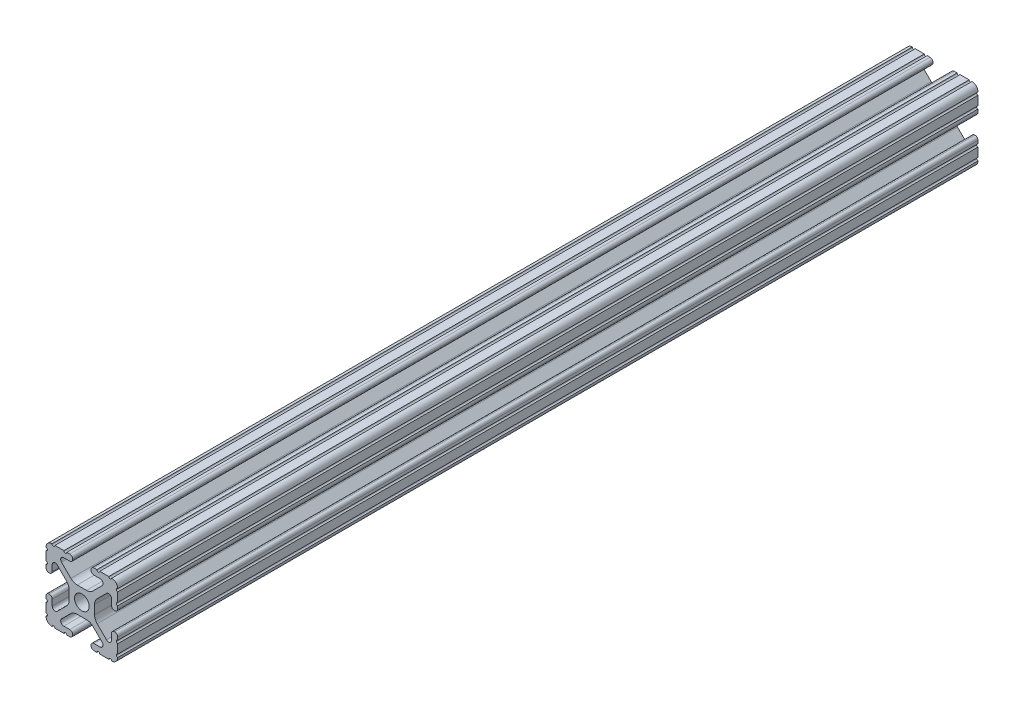
SolidWorks part; units mm, degrees
material "6061 Alloy"
ref_plane "Front Plane" through (0, 0, 0) normal (0, 0, 1) x (1, 0, 0)
ref_plane "Top Plane" through (0, 0, 0) normal (0, 1, 0) x (1, 0, 0)
ref_plane "Right Plane" through (0, 0, 0) normal (1, 0, 0) x (0, 0, -1)
sketch "Sketch1" plane through (0, 0, 0) normal (0, 0, 1) x (1, 0, 0)
  line L88 (-7.1797, -8.6452) -> (-3.9523, -5.4237)
  line L89 (-1.7093, -4.4958) -> (1.7093, -4.4958)
  line L90 (3.9523, -5.4237) -> (7.1797, -8.6452)
  line L91 (6.4164, -10.4902) -> (4.2875, -10.4902)
  line L92 (3.2385, -11.5392) -> (3.2385, -11.651)
  line L93 (4.2875, -12.7) -> (5.3171, -12.7)
  line L94 (6.3331, -12.7) -> (9.5504, -12.7)
  line L95 (12.7, -9.5504) -> (12.7, -6.3331)
  line L96 (12.7, -5.3171) -> (12.7, -4.2875)
  line L97 (11.651, -3.2385) -> (11.5392, -3.2385)
  line L98 (10.4902, -4.2875) -> (10.4902, -6.4021)
  line L99 (8.7371, -7.1294) -> (5.441, -3.8408)
  line L100 (4.5085, -1.5932) -> (4.5085, 1.5932)
  line L101 (5.441, 3.8408) -> (8.7371, 7.1294)
  line L102 (10.4902, 6.4021) -> (10.4902, 4.2875)
  line L103 (11.5392, 3.2385) -> (11.651, 3.2385)
  line L104 (12.7, 4.2875) -> (12.7, 5.3171)
  line L105 (12.7, 6.3331) -> (12.7, 9.5504)
  line L106 (9.5504, 12.7) -> (6.3331, 12.7)
  line L107 (5.3171, 12.7) -> (4.2875, 12.7)
  line L108 (3.2385, 11.651) -> (3.2385, 11.5392)
  line L109 (4.2875, 10.4902) -> (6.4768, 10.4902)
  line L110 (7.207, 8.7244) -> (3.8983, 5.4232)
  line L111 (1.6558, 4.4958) -> (-1.6558, 4.4958)
  line L112 (-3.8983, 5.4232) -> (-7.207, 8.7244)
  line L113 (-6.4768, 10.4902) -> (-4.2875, 10.4902)
  line L114 (-3.2385, 11.5392) -> (-3.2385, 11.651)
  line L115 (-4.2875, 12.7) -> (-5.3171, 12.7)
  line L116 (-6.3331, 12.7) -> (-9.5504, 12.7)
  line L117 (-12.7, 9.5504) -> (-12.7, 6.3331)
  line L118 (-12.7, 5.3171) -> (-12.7, 4.2875)
  line L119 (-11.651, 3.2385) -> (-11.5392, 3.2385)
  line L120 (-10.4902, 4.2875) -> (-10.4902, 6.4021)
  line L121 (-8.7371, 7.1294) -> (-5.441, 3.8408)
  line L122 (-4.5085, 1.5932) -> (-4.5085, -1.5932)
  line L123 (-5.441, -3.8408) -> (-8.7371, -7.1294)
  line L124 (-10.4902, -6.4021) -> (-10.4902, -4.2875)
  line L125 (-11.5392, -3.2385) -> (-11.651, -3.2385)
  line L126 (-12.7, -4.2875) -> (-12.7, -5.3171)
  line L127 (-12.7, -6.3331) -> (-12.7, -9.5504)
  line L128 (-9.5504, -12.7) -> (-6.3331, -12.7)
  line L129 (-5.3171, -12.7) -> (-4.2875, -12.7)
  line L130 (-3.2385, -11.651) -> (-3.2385, -11.5392)
  line L131 (-4.2875, -10.4902) -> (-6.4164, -10.4902)
  circle A1 centre (0, 0) radius 2.6035
  arc A104 (-7.1797, -8.6452) -> (-6.4164, -10.4902) centre (-6.4164, -9.4098) ccw
  arc A105 (-1.7093, -4.4958) -> (-3.9523, -5.4237) centre (-1.7093, -7.6708) ccw
  arc A106 (3.9523, -5.4237) -> (1.7093, -4.4958) centre (1.7093, -7.6708) ccw
  arc A107 (6.4164, -10.4902) -> (7.1797, -8.6452) centre (6.4164, -9.4098) ccw
  arc A108 (4.2875, -10.4902) -> (3.2385, -11.5392) centre (4.2875, -11.5392) ccw
  arc A109 (3.2385, -11.651) -> (4.2875, -12.7) centre (4.2875, -11.651) ccw
  arc A110 (6.3331, -12.7) -> (5.3171, -12.7) centre (5.8251, -12.7) ccw
  arc A111 (10.5664, -12.6998) -> (9.5504, -12.7) centre (10.0584, -12.7) ccw
  arc A112 (10.5664, -12.6998) -> (12.6998, -10.5664) centre (10.5918, -10.5918) ccw
  arc A113 (12.7, -9.5504) -> (12.6998, -10.5664) centre (12.7, -10.0584) ccw
  arc A114 (12.7, -5.3171) -> (12.7, -6.3331) centre (12.7, -5.8251) ccw
  arc A115 (12.7, -4.2875) -> (11.651, -3.2385) centre (11.651, -4.2875) ccw
  arc A116 (11.5392, -3.2385) -> (10.4902, -4.2875) centre (11.5392, -4.2875) ccw
  arc A117 (8.7371, -7.1294) -> (10.4902, -6.4021) centre (9.4628, -6.4021) ccw
  arc A118 (4.5085, -1.5932) -> (5.441, -3.8408) centre (7.6835, -1.5932) ccw
  arc A119 (5.441, 3.8408) -> (4.5085, 1.5932) centre (7.6835, 1.5932) ccw
  arc A120 (10.4902, 6.4021) -> (8.7371, 7.1294) centre (9.4628, 6.4021) ccw
  arc A121 (10.4902, 4.2875) -> (11.5392, 3.2385) centre (11.5392, 4.2875) ccw
  arc A122 (11.651, 3.2385) -> (12.7, 4.2875) centre (11.651, 4.2875) ccw
  arc A123 (12.7, 6.3331) -> (12.7, 5.3171) centre (12.7, 5.8251) ccw
  arc A124 (12.6998, 10.5664) -> (12.7, 9.5504) centre (12.7, 10.0584) ccw
  arc A125 (12.6998, 10.5664) -> (10.5664, 12.6998) centre (10.5918, 10.5918) ccw
  arc A126 (9.5504, 12.7) -> (10.5664, 12.6998) centre (10.0584, 12.7) ccw
  arc A127 (5.3171, 12.7) -> (6.3331, 12.7) centre (5.8251, 12.7) ccw
  arc A128 (4.2875, 12.7) -> (3.2385, 11.651) centre (4.2875, 11.651) ccw
  arc A129 (3.2385, 11.5392) -> (4.2875, 10.4902) centre (4.2875, 11.5392) ccw
  arc A130 (7.207, 8.7244) -> (6.4768, 10.4902) centre (6.4768, 9.4563) ccw
  arc A131 (1.6558, 4.4958) -> (3.8983, 5.4232) centre (1.6558, 7.6708) ccw
  arc A132 (-3.8983, 5.4232) -> (-1.6558, 4.4958) centre (-1.6558, 7.6708) ccw
  arc A133 (-6.4768, 10.4902) -> (-7.207, 8.7244) centre (-6.4768, 9.4563) ccw
  arc A134 (-4.2875, 10.4902) -> (-3.2385, 11.5392) centre (-4.2875, 11.5392) ccw
  arc A135 (-3.2385, 11.651) -> (-4.2875, 12.7) centre (-4.2875, 11.651) ccw
  arc A136 (-6.3331, 12.7) -> (-5.3171, 12.7) centre (-5.8251, 12.7) ccw
  arc A137 (-10.5664, 12.6998) -> (-9.5504, 12.7) centre (-10.0584, 12.7) ccw
  arc A138 (-10.5664, 12.6998) -> (-12.6998, 10.5664) centre (-10.5918, 10.5918) ccw
  arc A139 (-12.7, 9.5504) -> (-12.6998, 10.5664) centre (-12.7, 10.0584) ccw
  arc A140 (-12.7, 5.3171) -> (-12.7, 6.3331) centre (-12.7, 5.8251) ccw
  arc A141 (-12.7, 4.2875) -> (-11.651, 3.2385) centre (-11.651, 4.2875) ccw
  arc A142 (-11.5392, 3.2385) -> (-10.4902, 4.2875) centre (-11.5392, 4.2875) ccw
  arc A143 (-8.7371, 7.1294) -> (-10.4902, 6.4021) centre (-9.4628, 6.4021) ccw
  arc A144 (-4.5085, 1.5932) -> (-5.441, 3.8408) centre (-7.6835, 1.5932) ccw
  arc A145 (-5.441, -3.8408) -> (-4.5085, -1.5932) centre (-7.6835, -1.5932) ccw
  arc A146 (-10.4902, -6.4021) -> (-8.7371, -7.1294) centre (-9.4628, -6.4021) ccw
  arc A147 (-10.4902, -4.2875) -> (-11.5392, -3.2385) centre (-11.5392, -4.2875) ccw
  arc A148 (-11.651, -3.2385) -> (-12.7, -4.2875) centre (-11.651, -4.2875) ccw
  arc A149 (-12.7, -6.3331) -> (-12.7, -5.3171) centre (-12.7, -5.8251) ccw
  arc A150 (-12.6998, -10.5664) -> (-12.7, -9.5504) centre (-12.7, -10.0584) ccw
  arc A151 (-12.6998, -10.5664) -> (-10.5664, -12.6998) centre (-10.5918, -10.5918) ccw
  arc A152 (-9.5504, -12.7) -> (-10.5664, -12.6998) centre (-10.0584, -12.7) ccw
  arc A153 (-5.3171, -12.7) -> (-6.3331, -12.7) centre (-5.8251, -12.7) ccw
  arc A154 (-4.2875, -12.7) -> (-3.2385, -11.651) centre (-4.2875, -11.651) ccw
  arc A155 (-3.2385, -11.5392) -> (-4.2875, -10.4902) centre (-4.2875, -11.5392) ccw
extrude "Boss-Extrude1" add sketch "Sketch1" along normal mid plane 304.8
equation "\"deep\"= 6in"
equation "\"high\"= 20.5in"
equation "\"wide\"= 14in"
equation "\"Length@Boss-Extrude1\"      = \"wide\""
equation "\"front wide\"= 16in"
